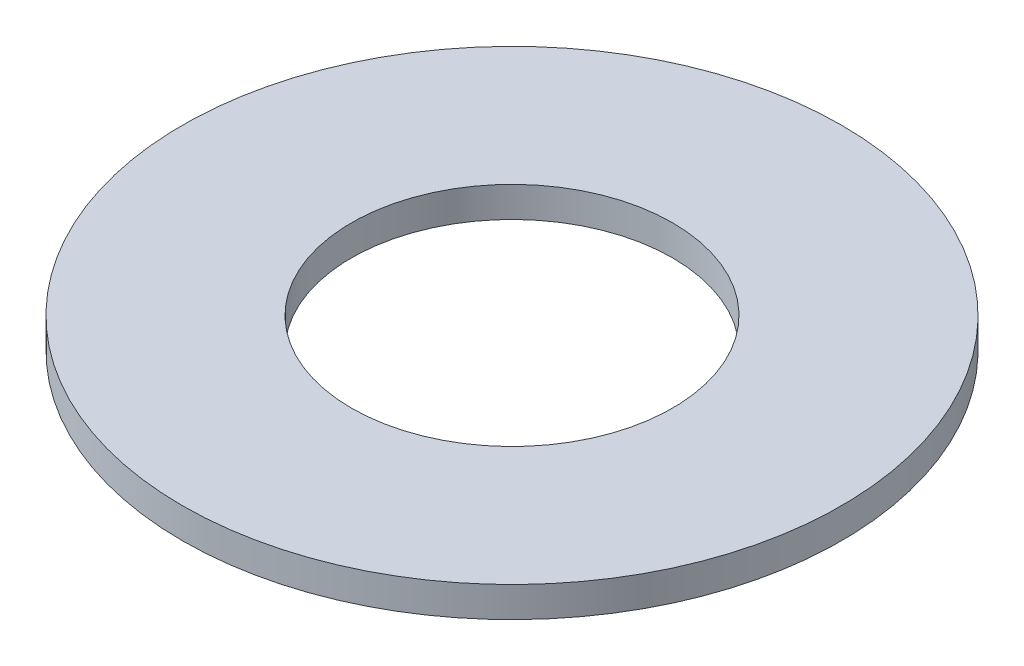
SolidWorks part; units mm, degrees
ref_plane "Front Plane" through (0, 0, 0) normal (0, 0, 1) x (1, 0, 0)
ref_plane "Top Plane" through (0, 0, 0) normal (0, 1, 0) x (1, 0, 0)
ref_plane "Right Plane" through (0, 0, 0) normal (1, 0, 0) x (0, 0, -1)
sketch "Sketch1" plane through (0, 0, 0) normal (0, 1, 0) x (1, 0, 0)
  circle A0 centre (0, 0) radius 97.5
  dimension "FLANGE_OD" = 195
extrude "Boss-Extrude1" add sketch "Sketch1" along normal blind 9
sketch "Sketch2" plane through (0, 0, 0) normal (0, 1, 0) x (1, 0, 0)
  circle A0 centre (0, 0) radius 47.5
  dimension "BORE_D" = 95
extrude "Cut-Extrude1" cut sketch "Sketch2" along normal through all
sketch "Sketch3" plane through (0, 9, 0) normal (0, 1, 0) x (1, 0, 0)
  circle A0 centre (0, 0) radius 26.9611 construction
  circle A1 centre (-26.9611, 0) radius 1.8028
  dimension "BOLT_D" = 3.6057
  dimension "BOLT_PCD" = 53.9222
extrude "Cut-Extrude2" cut sketch "Sketch3" against normal blind 7.0025 rebuild error yes
pattern_circular "CirPattern1" count 6 over 360 rebuild error yes
